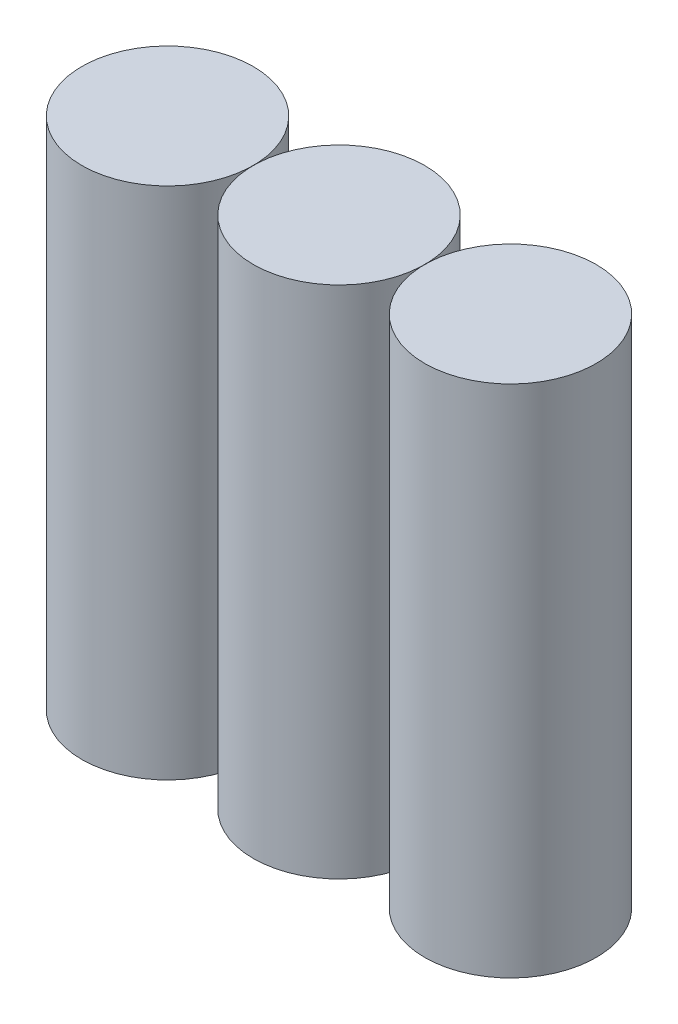
SolidWorks part; units mm, degrees
ref_plane "Front Plane" through (0, 0, 0) normal (0, 0, 1) x (1, 0, 0)
ref_plane "Top Plane" through (0, 0, 0) normal (0, 1, 0) x (1, 0, 0)
ref_plane "Right Plane" through (0, 0, 0) normal (1, 0, 0) x (0, 0, -1)
sketch "Sketch1" plane through (0, 0, 0) normal (0, 1, 0) x (1, 0, 0)
  line L0 (0, 0) -> (25.248, 0) construction
  circle A0 centre (0, 0) radius 2.5
  circle A2 centre (5, 0) radius 2.5
  circle A3 centre (-5, 0) radius 2.5
  point P8 (2.5, 0)
  point P10 (2.5, 0)
  point P11 (-2.5, 0)
  point P12 (-2.5, 0)
  point P13 (-7.5, 0)
  point P14 (7.5, 0)
  dimension "D1" = 5
  dimension "D2" = 5
  dimension "D3" = 5
extrude "Boss-Extrude1" add sketch "Sketch1" along normal blind 15 contours L0 A3 | A3 L0 | L0 A0 | A0 L0 | L0 A2 | A2 L0 region at (5, 0, -1.061) region at (0, 0, 2.4293) region at (-5, 0, 0) region at (5, 0, 1.061)
